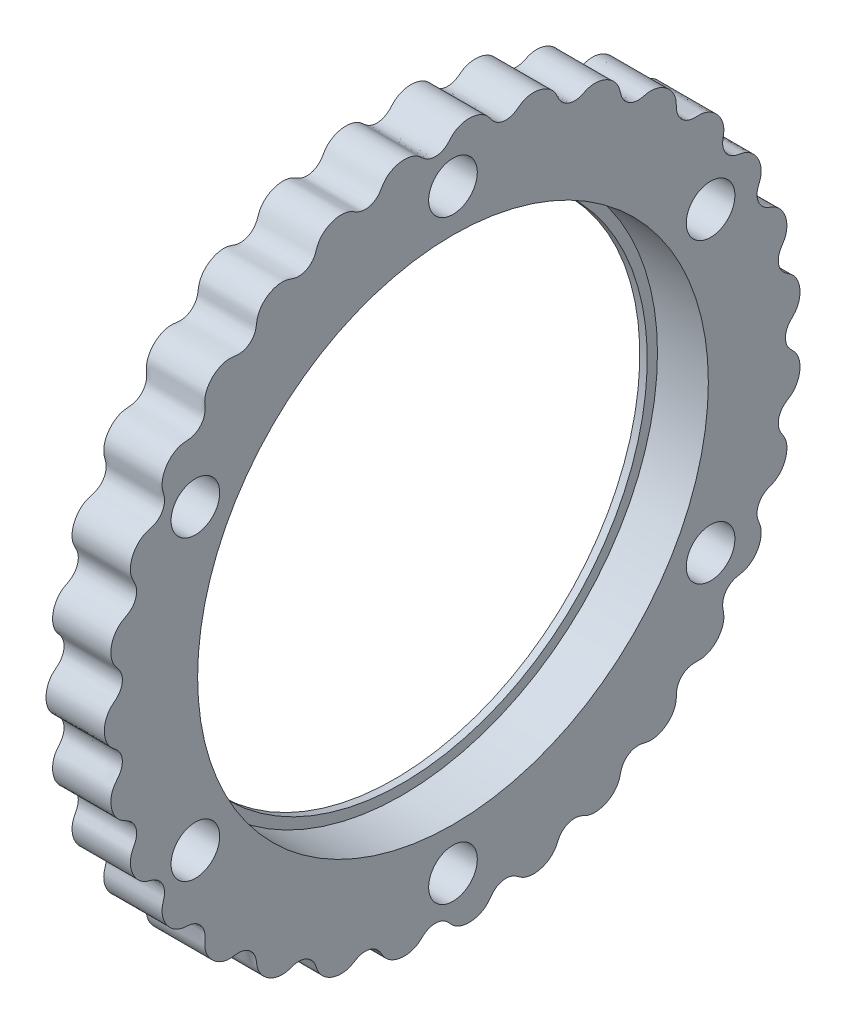
SolidWorks part; units mm, degrees
ref_plane "Front Plane" through (0, 0, 0) normal (0, 0, 1) x (1, 0, 0)
ref_plane "Top Plane" through (0, 0, 0) normal (0, 1, 0) x (1, 0, 0)
ref_plane "Right Plane" through (0, 0, 0) normal (1, 0, 0) x (0, 0, -1)
sketch "Sketch2" plane through (0, 0, 0) normal (0, 0, 1) x (1, 0, 0)
  line L0 (0, 0) -> (58.591, 0) construction
  line L2 (0, 0) -> (18.4, 0)
  line L3 (0, 0) -> (0, 2.5)
  line L4 (0, 2.5) -> (18.4, 2.5)
  line L5 (18.4, 0) -> (18.4, 2.5)
  line L6 (6.0094, 2.5) -> (6.0094, 6)
  line L11 (6.0094, 6) -> (9.9794, 6)
  line L16 (12.9794, 6) -> (12.9794, 3)
  line L17 (12.9794, 3) -> (13.6398, 3)
  line L18 (13.6398, 3) -> (13.6398, 2.5)
  line L19 (13.6398, 2.5) -> (6.0094, 2.5)
  line L22 (13.6398, 2.5) -> (16.1198, 2.5)
  line L23 (13.6398, 2.5) -> (13.6398, 4)
  line L24 (13.6398, 4) -> (16.1198, 4)
  line L25 (16.1198, 2.5) -> (16.1198, 4)
  line L27 (6.0094, 6) -> (9.9794, 6)
  line L28 (6.0094, 6) -> (6.0094, 9)
  line L29 (6.0094, 9) -> (9.9794, 9)
  line L30 (9.9794, 6) -> (9.9794, 9)
  line L31 (6.0094, 9) -> (6.0094, 8.25)
  line L32 (6.0094, 8.25) -> (5.0094, 8.25)
  line L33 (8.6609, 22.001) -> (8.6609, 12.476) construction
  line L34 (5.0094, 12.476) -> (12.3124, 12.476)
  line L35 (9.9794, 9) -> (12.3124, 9)
  line L36 (5.0094, 7.9375) -> (1.8344, 7.9375)
  line L37 (5.0094, 8.25) -> (5.0094, 12.476)
  line L38 (5.0094, 7.9375) -> (5.0094, 13.9365)
  line L39 (5.0094, 13.9365) -> (1.8344, 13.9365)
  line L40 (1.8344, 7.9375) -> (1.8344, 13.9365)
  line L41 (5.0094, 22.001) -> (12.3124, 22.001)
  line L42 (5.0094, 22.001) -> (5.0094, 30.1625)
  line L43 (5.0094, 30.1625) -> (12.3124, 30.1625)
  line L44 (12.3124, 22.001) -> (12.3124, 30.1625)
  line L49 (16.6398, 22.001) -> (16.6398, 7.5)
  line L51 (23.0198, 7.5) -> (23.0198, 6.5)
  line L54 (16.1198, 4) -> (13.6398, 4)
  line L56 (18.0398, 7.5) -> (23.0198, 7.5)
  line L57 (13.3124, 22.001) -> (16.6398, 22.001)
  line L58 (16.1198, 3.5) -> (20.0198, 3.5)
  line L59 (29.9098, 14) -> (26.9098, 11)
  line L60 (4.0094, 31.75) -> (18.0398, 31.75)
  line L61 (18.0398, 7.5) -> (23.0198, 7.5)
  line L62 (18.0398, 7.5) -> (18.0398, 12)
  line L63 (18.0398, 12) -> (23.0198, 12)
  line L64 (23.0198, 7.5) -> (23.0198, 12)
  line L65 (18.0398, 31.75) -> (18.0398, 12)
  line L66 (23.0198, 11) -> (26.9098, 11)
  line L67 (34.8098, 23) -> (31.3098, 19.5)
  line L68 (35.8098, 31) -> (38.7998, 33.99)
  line L69 (29.9098, 14) -> (29.9098, 15)
  line L70 (29.9098, 15) -> (22.9398, 15)
  line L71 (22.9398, 15) -> (21.0398, 15)
  line L72 (18.0398, 7.5) -> (16.6398, 7.5)
  line L73 (21.0398, 15) -> (21.0398, 43)
  line L74 (19.5798, 40) -> (9.6198, 40)
  line L75 (9.6198, 40) -> (4.0094, 40)
  line L76 (21.0398, 43) -> (19.5798, 43)
  line L77 (22.9398, 15) -> (29.9098, 15)
  line L78 (22.9398, 15) -> (22.9398, 21)
  line L79 (22.9398, 21) -> (29.9098, 21)
  line L80 (29.9098, 15) -> (29.9098, 21)
  line L81 (9.6198, 40) -> (19.5798, 40)
  line L82 (9.6198, 40) -> (9.6198, 50)
  line L83 (9.6198, 50) -> (19.5798, 50)
  line L84 (19.5798, 40) -> (19.5798, 50)
  line L85 (4.0094, 40) -> (4.0094, 31.75)
  line L86 (12.9794, 3) -> (12.9794, 2.5)
  line L87 (31.3098, 19.5) -> (29.9098, 19.5)
  line L88 (21.4694, 63.5) -> (21.4694, 51.308)
  line L89 (21.4694, 63.5) -> (25.9398, 63.5)
  line L90 (25.9398, 63.5) -> (25.9398, 25)
  line L91 (27.8398, 25) -> (25.9398, 25)
  line L92 (9.6198, 48) -> (8.1598, 48)
  line L93 (8.1598, 48) -> (8.1598, 53.476)
  line L94 (8.1598, 53.476) -> (19.5798, 53.476)
  line L95 (19.5798, 53.476) -> (19.5798, 50)
  line L96 (13.8698, 63.001) -> (13.8698, 53.476) construction
  line L97 (8.1598, 63.001) -> (19.5798, 63.001)
  line L98 (8.1598, 63.001) -> (8.1598, 68.2625)
  line L99 (8.1598, 68.2625) -> (19.5798, 68.2625)
  line L100 (19.5798, 63.001) -> (19.5798, 68.2625)
  line L101 (12.9794, 6) -> (11.9794, 6)
  line L102 (8.1598, 44.825) -> (4.9848, 44.825)
  line L103 (8.1598, 44.825) -> (8.1598, 54.9365)
  line L104 (8.1598, 54.9365) -> (4.9848, 54.9365)
  line L106 (9.9794, 6) -> (10.8794, 6)
  line L107 (27.8398, 25) -> (34.8098, 25)
  line L108 (34.8098, 25) -> (34.8098, 23)
  line L109 (0, 0) -> (-2, 0)
  line L110 (0, 0) -> (0, 11)
  line L111 (27.8398, 25) -> (34.8098, 25)
  line L112 (27.8398, 25) -> (27.8398, 32.5)
  line L113 (27.8398, 32.5) -> (34.8098, 32.5)
  line L114 (34.8098, 25) -> (34.8098, 32.5)
  line L115 (35.8098, 31) -> (34.8098, 31)
  line L116 (27.8398, 32.5) -> (27.8398, 64.5)
  line L117 (20.5373, 74.025) -> (6.2023, 74.025)
  line L118 (6.2023, 74.025) -> (6.2023, 76.2)
  line L119 (38.7998, 47.29) -> (30.8398, 55.25)
  line L120 (0, 11) -> (-2, 11)
  line L121 (38.7998, 43.815) -> (30.8623, 43.815)
  line L123 (-4.8152, 69.85) -> (1.5348, 76.2)
  line L124 (38.7998, 47.29) -> (38.7998, 33.99)
  line L125 (-2, 0) -> (-2, 11)
  line L126 (38.7998, 37.465) -> (30.8623, 37.465)
  line L127 (30.8623, 43.815) -> (30.8623, 37.465)
  line L128 (6.0094, 2.5) -> (6.0094, 0)
  line L129 (-0.0152, 63.5) -> (-0.0152, 30)
  line L132 (4.9848, 63.5) -> (-0.0152, 63.5)
  line L136 (-1.8152, 30) -> (-11.7752, 30)
  line L138 (-13.7752, 25.4) -> (-2, 25.4)
  line L139 (-2, 25.4) -> (-2, 11.5)
  line L140 (27.8398, 64.5) -> (20.5373, 64.5)
  line L141 (-1.8152, 30) -> (-11.7752, 30)
  line L142 (-1.8152, 30) -> (-1.8152, 39)
  line L143 (-1.8152, 39) -> (-11.7752, 39)
  line L144 (-11.7752, 30) -> (-11.7752, 39)
  line L145 (20.5373, 64.5) -> (20.5373, 74.025)
  line L146 (-12.7752, 37) -> (-12.7752, 47.29)
  line L147 (-12.7752, 37) -> (-11.7752, 37)
  line L148 (30.8398, 55.25) -> (30.8398, 76.2)
  line L149 (11.9794, 6) -> (11.9794, 5.45)
  line L154 (-2, 11.5) -> (0.5, 11.5)
  line L155 (4.9848, 60.6197) -> (24.0348, 60.6197)
  line L160 (4.9848, 60.6197) -> (4.9848, 55.8572)
  line L161 (4.9848, 55.8572) -> (24.0348, 55.8572)
  line L166 (24.0348, 60.6197) -> (24.0348, 55.8572)
  line L167 (4.9848, 60.6197) -> (24.0348, 55.8572) construction
  line L172 (4.9848, 55.8572) -> (24.0348, 60.6197) construction
  line L173 (24.0348, 62.2072) -> (25.9398, 62.2072)
  line L174 (11.9794, 5.45) -> (10.8794, 5.45)
  line L175 (10.8794, 6) -> (10.8794, 5.45)
  line L176 (24.0348, 62.2072) -> (24.0348, 54.2697)
  line L177 (24.0348, 54.2697) -> (25.9398, 54.2697)
  line L178 (25.9398, 62.2072) -> (25.9398, 54.2697)
  line L179 (24.0348, 62.2072) -> (25.9398, 54.2697) construction
  line L180 (24.0348, 54.2697) -> (25.9398, 62.2072) construction
  line L181 (3, 19.6197) -> (15.7, 19.6197)
  line L182 (3, 19.6197) -> (3, 14.8572)
  line L183 (3, 14.8572) -> (15.7, 14.8572)
  line L184 (15.7, 19.6197) -> (15.7, 14.8572)
  line L185 (3, 19.6197) -> (15.7, 14.8572) construction
  line L186 (3, 14.8572) -> (15.7, 19.6197) construction
  line L187 (15.7, 21.2072) -> (16.6398, 21.2072)
  line L188 (15.7, 21.2072) -> (15.7, 13.2697)
  line L189 (15.7, 13.2697) -> (16.6398, 13.2697)
  line L190 (16.6398, 21.2072) -> (16.6398, 13.2697)
  line L191 (15.7, 21.2072) -> (16.6398, 13.2697) construction
  line L192 (15.7, 13.2697) -> (16.6398, 21.2072) construction
  line L193 (0.5, 11.5) -> (0.5, 6.9375)
  line L194 (0.5, 6.9375) -> (1.8344, 6.9375)
  line L195 (23.0198, 6.5) -> (20.0198, 3.5)
  line L196 (4.9848, 63.5) -> (4.9848, 54.9365)
  line L197 (3, 43.825) -> (4.9848, 43.825)
  line L198 (1.8344, 6.9375) -> (1.8344, 7.9375)
  line L199 (6.0094, 0) -> (12.9794, 0)
  line L200 (12.9794, 0) -> (12.9794, 2.5)
  line L201 (18.0398, 31.75) -> (18.0398, 35.875)
  line L202 (18.0398, 35.875) -> (21.0398, 35.875)
  line L203 (30.8398, 76.2) -> (6.2023, 76.2)
  line L204 (2.7573, 69.85) -> (7.2023, 69.85) construction
  line L205 (7.2023, 67.4688) -> (26.2523, 67.4688)
  line L206 (7.2023, 74.025) -> (7.2023, 64.5)
  line L207 (7.2023, 64.5) -> (-1.8152, 64.5)
  line L208 (-1.8152, 64.5) -> (-1.8152, 39)
  line L209 (-12.7752, 47.29) -> (-4.8152, 55.25)
  line L210 (-4.8152, 55.25) -> (-4.8152, 69.85)
  line L211 (7.2023, 67.4688) -> (7.2023, 72.2312)
  line L212 (7.2023, 72.2312) -> (26.2523, 72.2313)
  line L213 (26.2523, 67.4688) -> (26.2523, 72.2313)
  line L214 (26.2523, 73.8187) -> (30.8398, 73.8187)
  line L215 (26.2523, 73.8187) -> (26.2523, 65.8813)
  line L216 (26.2523, 65.8813) -> (30.8398, 65.8813)
  line L217 (30.8398, 73.8187) -> (30.8398, 65.8813)
  line L218 (2.7573, 72.2313) -> (24.9823, 72.2313)
  line L219 (2.7573, 72.2313) -> (2.7573, 67.4687)
  line L220 (2.7573, 67.4687) -> (24.9823, 67.4687)
  line L221 (24.9823, 72.2313) -> (24.9823, 67.4687)
  line L222 (24.9823, 69.85) -> (20.5373, 69.85) construction
  line L223 (21.4694, 51.308) -> (22.9398, 51.308)
  line L224 (22.9398, 51.308) -> (22.9398, 21)
  line L225 (13.6398, 4) -> (13.6398, 12.2697)
  line L226 (13.6398, 12.2697) -> (13.3124, 12.2697)
  line L227 (13.3124, 12.2697) -> (13.3124, 22.001)
  line L228 (12.3124, 9) -> (12.3124, 12.476)
  line L229 (-1.8152, 30) -> (-0.0152, 30)
  line L230 (8.1598, 65.6317) -> (2.7573, 65.6317) construction
  line L231 (19.5798, 65.6317) -> (24.9823, 65.6317) construction
  line L232 (1.5348, 76.2) -> (6.2023, 76.2)
  line L233 (-11.7752, 30) -> (-13.7752, 30)
  line L234 (-13.7752, 30) -> (-13.7752, 25.4)
  line L235 (3, 13.9365) -> (3, 43.825)
  line L236 (4.9848, 54.9365) -> (4.9848, 44.825)
  line L237 (4.9848, 43.825) -> (4.9848, 44.825)
  circle A0 centre (26.8898, 25.95) radius 0.95
  circle A1 centre (21.9898, 15.95) radius 0.95
  circle A2 centre (17.3398, 8.2) radius 0.7
  circle A3 centre (10.4294, 6.45) radius 0.45
  circle A4 centre (-0.9152, 30.9) radius 0.9
  point P7 (24.9873, 58.2385)
  point P131 (16.1699, 17.2385)
  point P135 (14.5098, 58.2385)
  point P146 (9.35, 17.2385)
sketch "Sketch3" plane through (0, 0, 0) normal (1, 0, 0) x (0, 0, -1)
  line L0 (0, 0) -> (0, 69.85) construction
  line L1 (0, 0) -> (13.6271, 68.5079) construction
  line L2 (0, 0) -> (0, 58.2385) construction
  line L3 (0, 0) -> (50.436, 29.1192) construction
  line L4 (0, 0) -> (0, 31.75) construction
  line L5 (0, 0) -> (12.1502, 29.3332) construction
  line L6 (0, 0) -> (0, 17.2385) construction
  line L7 (0, 0) -> (14.929, 8.6192) construction
  line L8 (0, 0) -> (0, 58.2385) construction
  line L9 (0, 0) -> (50.436, 29.1192) construction
  line L10 (0, 0) -> (5.9583, 29.9542) construction
  line L11 (0, 0) -> (16.9677, 25.394) construction
  circle A0 centre (0, 0) radius 69.85 construction
  circle A1 centre (0, 0) radius 58.2385 construction
  circle A2 centre (0, 0) radius 31.75 construction
  circle A3 centre (0, 0) radius 17.2385 construction
  circle A4 centre (0, 69.85) radius 3.175
  circle A5 centre (0, 58.2385) radius 4.7625
  circle A6 centre (0, 31.75) radius 3.175
  circle A7 centre (0, 17.2385) radius 4.7625
  circle A8 centre (13.6271, 68.5079) radius 3.175
  circle A9 centre (26.7304, 64.533) radius 3.175
  circle A10 centre (38.8066, 58.0782) radius 3.175
  circle A11 centre (49.3914, 49.3914) radius 3.175
  circle A12 centre (58.0782, 38.8066) radius 3.175
  circle A13 centre (64.533, 26.7304) radius 3.175
  circle A14 centre (68.5079, 13.6271) radius 3.175
  circle A15 centre (69.85, 0) radius 3.175
  circle A16 centre (68.5079, -13.6271) radius 3.175
  circle A17 centre (64.533, -26.7304) radius 3.175
  circle A18 centre (58.0782, -38.8066) radius 3.175
  circle A19 centre (49.3914, -49.3914) radius 3.175
  circle A20 centre (38.8066, -58.0782) radius 3.175
  circle A21 centre (26.7304, -64.533) radius 3.175
  circle A22 centre (13.6271, -68.5079) radius 3.175
  circle A23 centre (0, -69.85) radius 3.175
  circle A24 centre (-13.6271, -68.5079) radius 3.175
  circle A25 centre (-26.7304, -64.533) radius 3.175
  circle A26 centre (-38.8066, -58.0782) radius 3.175
  circle A27 centre (-49.3914, -49.3914) radius 3.175
  circle A28 centre (-58.0782, -38.8066) radius 3.175
  circle A29 centre (-64.533, -26.7304) radius 3.175
  circle A30 centre (-68.5079, -13.6271) radius 3.175
  circle A31 centre (-69.85, 0) radius 3.175
  circle A32 centre (-68.5079, 13.6271) radius 3.175
  circle A33 centre (-64.533, 26.7304) radius 3.175
  circle A34 centre (-58.0782, 38.8066) radius 3.175
  circle A35 centre (-49.3914, 49.3914) radius 3.175
  circle A36 centre (-38.8066, 58.0782) radius 3.175
  circle A37 centre (-26.7304, 64.533) radius 3.175
  circle A38 centre (-13.6271, 68.5079) radius 3.175
  circle A47 centre (50.436, 29.1192) radius 4.7625
  circle A48 centre (50.436, -29.1192) radius 4.7625
  circle A49 centre (0, -58.2385) radius 4.7625
  circle A50 centre (-50.436, -29.1192) radius 4.7625
  circle A51 centre (-50.436, 29.1192) radius 4.7625
  circle A58 centre (12.1502, 29.3332) radius 3.175
  circle A59 centre (22.4506, 22.4506) radius 3.175
  circle A60 centre (29.3332, 12.1502) radius 3.175
  circle A61 centre (31.75, 0) radius 3.175
  circle A62 centre (29.3332, -12.1502) radius 3.175
  circle A63 centre (22.4506, -22.4506) radius 3.175
  circle A64 centre (12.1502, -29.3332) radius 3.175
  circle A65 centre (0, -31.75) radius 3.175
  circle A66 centre (-12.1502, -29.3332) radius 3.175
  circle A67 centre (-22.4506, -22.4506) radius 3.175
  circle A68 centre (-29.3332, -12.1502) radius 3.175
  circle A69 centre (-31.75, 0) radius 3.175
  circle A70 centre (-29.3332, 12.1502) radius 3.175
  circle A71 centre (-22.4506, 22.4506) radius 3.175
  circle A72 centre (14.929, 8.6192) radius 4.7625
  circle A73 centre (14.929, -8.6192) radius 4.7625
  circle A74 centre (0, -17.2385) radius 4.7625
  circle A75 centre (-14.929, -8.6192) radius 4.7625
  circle A76 centre (-14.929, 8.6192) radius 4.7625
  circle A77 centre (0, 0) radius 50
  circle A78 centre (0, 0) radius 9
  circle A79 centre (-12.1502, 29.3332) radius 3.175
  circle A80 centre (0, 0) radius 76.2
  circle A81 centre (0, 0) radius 74.025
  circle A82 centre (0, 69.85) radius 3.9687
  circle A83 centre (49.3914, 49.3914) radius 3.9687
  circle A84 centre (69.85, 0) radius 3.9688
  circle A85 centre (49.3914, -49.3914) radius 3.9687
  circle A86 centre (0, -69.85) radius 3.9687
  circle A87 centre (-49.3914, -49.3914) radius 3.9687
  circle A88 centre (-69.85, 0) radius 3.9688
  circle A89 centre (-49.3914, 49.3914) radius 3.9687
  circle A90 centre (0, 69.85) radius 2.3812
  circle A91 centre (13.6271, 68.5079) radius 2.3812
  circle A92 centre (26.7304, 64.533) radius 2.3813
  circle A93 centre (38.8066, 58.0782) radius 2.3812
  circle A94 centre (49.3914, 49.3914) radius 2.3812
  circle A95 centre (58.0782, 38.8066) radius 2.3812
  circle A96 centre (64.533, 26.7304) radius 2.3813
  circle A97 centre (68.5079, 13.6271) radius 2.3813
  circle A98 centre (69.85, 0) radius 2.3813
  circle A99 centre (68.5079, -13.6271) radius 2.3813
  circle A100 centre (64.533, -26.7304) radius 2.3813
  circle A101 centre (58.0782, -38.8066) radius 2.3812
  circle A102 centre (49.3914, -49.3914) radius 2.3812
  circle A103 centre (38.8066, -58.0782) radius 2.3812
  circle A104 centre (26.7304, -64.533) radius 2.3813
  circle A105 centre (13.6271, -68.5079) radius 2.3812
  circle A106 centre (0, -69.85) radius 2.3812
  circle A107 centre (-13.6271, -68.5079) radius 2.3812
  circle A108 centre (-26.7304, -64.533) radius 2.3813
  circle A109 centre (-38.8066, -58.0782) radius 2.3812
  circle A110 centre (-49.3914, -49.3914) radius 2.3812
  circle A111 centre (-58.0782, -38.8066) radius 2.3812
  circle A112 centre (-64.533, -26.7304) radius 2.3812
  arc A113 (3.0399, 30.8338) -> (8.9911, 29.65) centre (5.9583, 29.9542) cw
  arc A114 (14.6081, 27.3234) -> (19.6532, 23.9523) centre (16.9677, 25.394) cw
  arc A115 (23.9523, 19.6532) -> (27.3234, 14.6081) centre (25.394, 16.9677) cw
  arc A116 (29.65, 8.9911) -> (30.8338, 3.0399) centre (29.9542, 5.9583) cw
  arc A117 (30.8338, -3.0399) -> (29.65, -8.9911) centre (29.9542, -5.9583) cw
  arc A118 (27.3234, -14.6081) -> (23.9523, -19.6532) centre (25.394, -16.9677) cw
  arc A119 (19.6532, -23.9523) -> (14.6081, -27.3234) centre (16.9677, -25.394) cw
  arc A120 (8.9911, -29.65) -> (3.0399, -30.8338) centre (5.9583, -29.9542) cw
  arc A121 (-3.0399, -30.8338) -> (-8.9911, -29.65) centre (-5.9583, -29.9542) cw
  arc A122 (-14.6081, -27.3234) -> (-19.6532, -23.9523) centre (-16.9677, -25.394) cw
  arc A123 (-23.9523, -19.6532) -> (-27.3234, -14.6081) centre (-25.394, -16.9677) cw
  arc A124 (-29.65, -8.9911) -> (-30.8338, -3.0399) centre (-29.9542, -5.9583) cw
  arc A125 (-30.8338, 3.0399) -> (-29.65, 8.9911) centre (-29.9542, 5.9583) cw
  arc A126 (-27.3234, 14.6081) -> (-23.9523, 19.6532) centre (-25.394, 16.9677) cw
  arc A127 (-19.6532, 23.9523) -> (-14.6081, 27.3234) centre (-16.9677, 25.394) cw
  arc A128 (-8.9911, 29.65) -> (-3.0399, 30.8338) centre (-5.9583, 29.9542) cw
  arc A129 (26.9875, 0) -> (26.9932, 0.1932) centre (30.2705, 0) cw
  arc A130 (65.0988, 0.2771) -> (65.0875, 0) centre (68.4964, 0) ccw
  circle A131 centre (1.5875, 0) radius 40
  circle A132 centre (1.5875, 0) radius 2.5
  circle A133 centre (1.5875, 0) radius 3
  circle A134 centre (1.5875, 0) radius 43
  circle A135 centre (-68.5079, -13.6271) radius 2.3813
  circle A136 centre (-69.85, 0) radius 2.3813
  circle A137 centre (-68.5079, 13.6271) radius 2.3813
  circle A138 centre (-64.533, 26.7304) radius 2.3812
  circle A139 centre (-58.0782, 38.8066) radius 2.3812
  circle A140 centre (-49.3914, 49.3914) radius 2.3812
  circle A141 centre (-38.8066, 58.0782) radius 2.3812
  circle A142 centre (-26.7304, 64.533) radius 2.3813
  circle A143 centre (-13.6271, 68.5079) radius 2.3812
  circle A144 centre (0, 58.2385) radius 2.3812
  circle A145 centre (0, 58.2385) radius 3.9688
  circle A146 centre (50.436, 29.1192) radius 3.9688
  circle A147 centre (50.436, 29.1192) radius 2.3813
  circle A148 centre (50.436, -29.1192) radius 3.9687
  circle A149 centre (50.436, -29.1192) radius 2.3812
  circle A150 centre (0, -58.2385) radius 3.9687
  circle A151 centre (0, -58.2385) radius 2.3812
  circle A152 centre (-50.436, -29.1192) radius 3.9687
  circle A153 centre (-50.436, -29.1192) radius 2.3812
  circle A154 centre (-50.436, 29.1192) radius 3.9687
  circle A155 centre (-50.436, 29.1192) radius 2.3812
  spline S1 degree 4 number of poles 499 (26.9875, 0) -> (26.9932, 0.1932)
  spline S3 degree 4 number of poles 617 (65.0875, 0) -> (65.0988, 0.2771)
  point P116 (0, 0)
  point P225 (0, 0)
sketch "Sketch6" plane through (0, 0, 0) normal (0, 0, 1) x (1, 0, 0)
  line L0 (19.5798, 53.476) -> (19.5798, 50) construction
  line L1 (9.6198, 50) -> (19.5798, 50) construction
  line L2 (9.6198, 40) -> (9.6198, 50) construction
  line L3 (9.6198, 48) -> (8.1598, 48) construction
  line L4 (8.1598, 48) -> (8.1598, 53.476) construction
  line L5 (8.1598, 53.476) -> (19.5798, 53.476) construction
  line L6 (19.5798, 53.476) -> (19.5798, 50)
  line L7 (9.6198, 50) -> (19.5798, 50)
  line L8 (9.6198, 48) -> (9.6198, 50)
  line L9 (9.6198, 48) -> (8.1598, 48)
  line L10 (8.1598, 48) -> (8.1598, 53.476)
  line L11 (8.1598, 53.476) -> (19.5798, 53.476)
revolve "Revolve2" add sketch "Sketch6" angle 360 about L0
sketch "Sketch7" plane through (0, 0, 0) normal (1, 0, 0) x (0, 0, -1)
  circle A0 centre (0, 0) radius 50 construction
  circle A1 centre (-50.436, -29.1192) radius 4.7625 construction
  circle A2 centre (0, -58.2385) radius 4.7625 construction
  circle A3 centre (50.436, -29.1192) radius 4.7625 construction
  circle A4 centre (50.436, 29.1192) radius 4.7625 construction
  circle A5 centre (0, 58.2385) radius 4.7625 construction
  circle A6 centre (-50.436, 29.1192) radius 4.7625 construction
  circle A7 centre (0, 0) radius 50
  circle A8 centre (-50.436, -29.1192) radius 4.7625
  circle A9 centre (0, -58.2385) radius 4.7625
  circle A10 centre (50.436, -29.1192) radius 4.7625
  circle A11 centre (50.436, 29.1192) radius 4.7625
  circle A12 centre (0, 58.2385) radius 4.7625
  circle A13 centre (-50.436, 29.1192) radius 4.7625
  arc A14 (65.0988, 0.2771) -> (65.0875, 0) centre (68.4964, 0) ccw construction
  arc A15 (65.0988, 0.2771) -> (65.0875, 0) centre (68.4964, 0) ccw
  spline S0 degree 4 number of poles 617 (65.0875, 0) -> (65.0988, 0.2771) construction
  spline S1 degree 4 number of poles 617 (65.0875, 0) -> (65.0988, 0.2771)
extrude "Boss-Extrude1" add sketch "Sketch7" along normal up to vertex (19.5798 mm away) from vertex up to point (19.5798, 68.2625, 0) starting at point (8.1598, 68.2625, 0)
